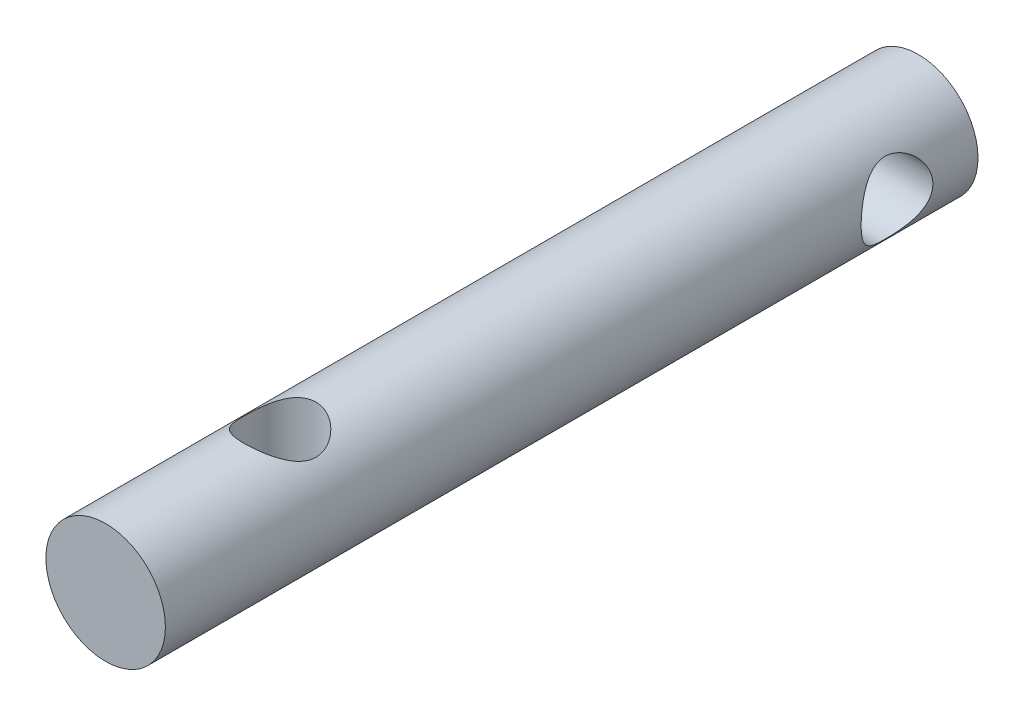
SolidWorks part; units mm, degrees
ref_plane "Front Plane" through (0, 0, 0) normal (0, 0, 1) x (1, 0, 0)
ref_plane "Top Plane" through (0, 0, 0) normal (0, 1, 0) x (1, 0, 0)
ref_plane "Right Plane" through (0, 0, 0) normal (1, 0, 0) x (0, 0, -1)
sketch "Sketch1" plane through (0, 0, 0) normal (0, 0, 1) x (1, 0, 0)
  circle A0 centre (0, 0) radius 3.175
  dimension "D1" = 6.35
extrude "Boss-Extrude1" add sketch "Sketch1" along normal blind 43.18 contours A0
sketch "Sketch2" plane through (0, 0, 0) normal (0, 1, 0) x (1, 0, 0)
  line L0 (-3.175, -43.18) -> (3.175, -43.18) construction
  line L1 (0, -43.18) -> (0, 0) construction
  circle A0 centre (0, -33.909) radius 1.905
  dimension "D2" = 3.81
  dimension "D1" = 9.271
extrude "Cut-Extrude1" cut sketch "Sketch2" against normal through all and the other way through all
sketch "Sketch3" plane through (0, 0, 0) normal (1, 0, 0) x (0, 0, -1)
  circle A0 centre (-4.3031, 0) radius 1.905
  dimension "D2" = 3.81
  dimension "D1" = 4.3031
extrude "Cut-Extrude2" cut sketch "Sketch3" against normal through all and the other way through all
